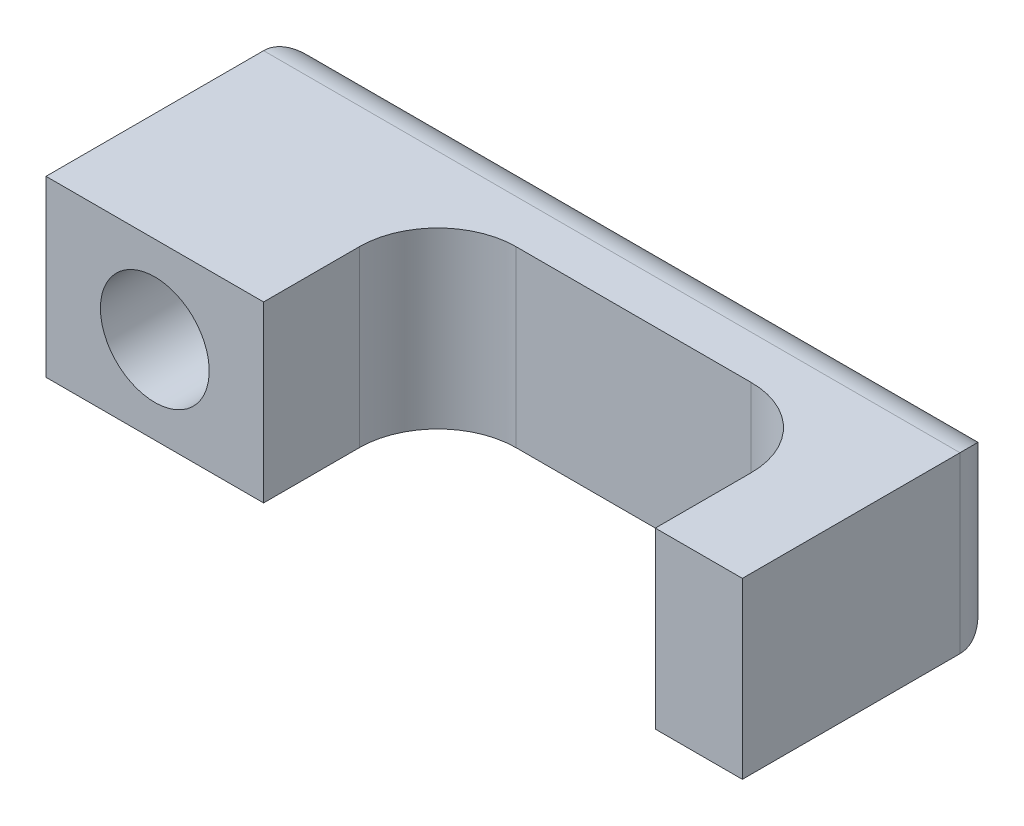
SolidWorks part; units mm, degrees
ref_plane "Front Plane" through (0, 0, 0) normal (0, 0, 1) x (1, 0, 0)
ref_plane "Top Plane" through (0, 0, 0) normal (0, 1, 0) x (1, 0, 0)
ref_plane "Right Plane" through (0, 0, 0) normal (1, 0, 0) x (0, 0, -1)
sketch "Side" plane through (0, 0, 0) normal (0, 1, 0) x (1, 0, 0)
  line L1 (0, 0) -> (16, 0)
  line L2 (0, 0) -> (0, 6)
  line L3 (0, 6) -> (16, 6)
  line L4 (16, 0) -> (16, 6)
  dimension "D1" = 16
  dimension "D2" = 6
extrude "Side_Ex" add sketch "Side" along normal blind 4
sketch "Wire" plane through (0, 0, 0) normal (0, 1, 0) x (1, 0, 0)
  line L0 (0, 0) -> (16, 0) construction
  line L1 (12.2, 4) -> (6.8, 4)
  line L2 (14, 2.2) -> (14, 0)
  line L3 (14, 0) -> (5, 0)
  line L4 (5, 2.2) -> (5, 0)
  line L5 (0, 6) -> (0, 0) construction
  line L7 (16, 0) -> (16, 6) construction
  line L8 (16, 6) -> (0, 6) construction
  arc A0 (14, 2.2) -> (12.2, 4) centre (12.2, 2.2) ccw
  arc A1 (5, 2.2) -> (6.8, 4) centre (6.8, 2.2) cw
  dimension "D4" = 1.8
  dimension "D5" = 1.8
  dimension "D1" = 5
  dimension "D2" = 2
  dimension "D3" = 2
ref_plane "Plane1" through (0, 0, -6) normal (0, 0, -1) x (-1, 0, 0)
sketch "Hole" plane through (0, 0, -6) normal (0, 0, -1) x (-1, 0, 0)
  line L0 (0, 4) -> (0, 0) construction
  line L1 (-16, 4) -> (0, 4) construction
  circle A0 centre (-2.5, 2) radius 1.25
  dimension "D1" = 2.5
  dimension "D3" = 2.5
  dimension "D2" = 2
extrude "Hole_Cut" cut sketch "Hole" against normal through all
extrude "Wire_Cut" cut sketch "Wire" along normal through all
fillet "Fillet1" radius 1 4 edges at (16, 2, -6) (8, 4, -6) (8, 0, -6) (0, 2, -6)
